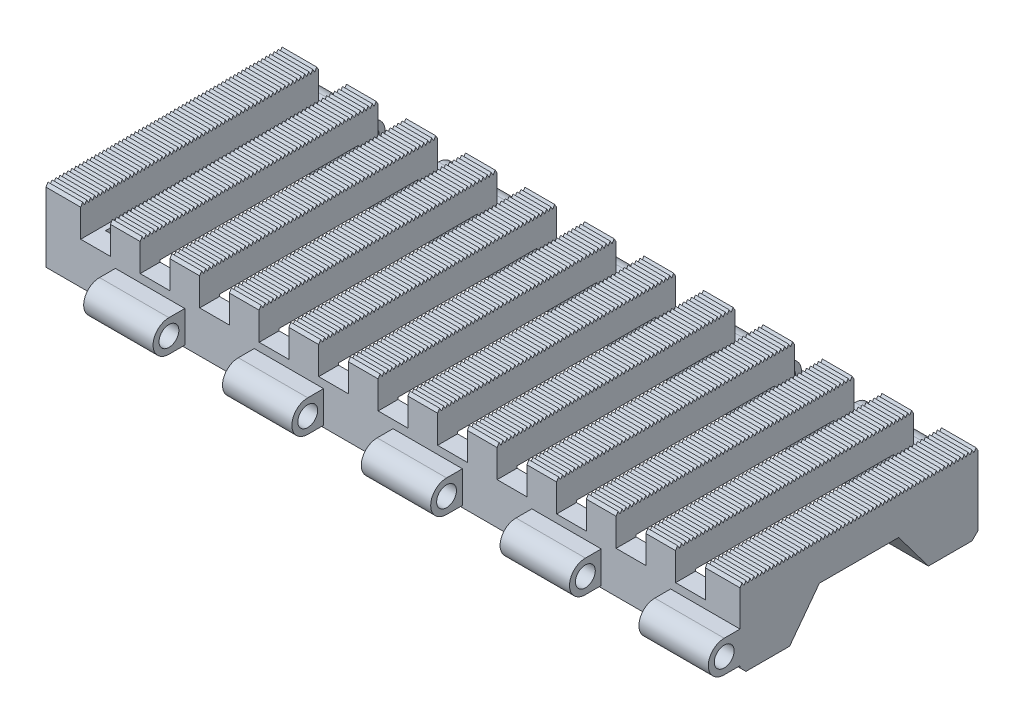
SolidWorks part; units mm, degrees
material "POM Acetal Copolymer"
ref_plane "Front Plane" through (0, 0, 0) normal (0, 0, 1) x (1, 0, 0)
ref_plane "Top Plane" through (0, 0, 0) normal (0, 1, 0) x (1, 0, 0)
ref_plane "Right Plane" through (0, 0, 0) normal (1, 0, 0) x (0, 0, -1)
sketch "Sketch1" plane through (0, 0, 0) normal (1, 0, 0) x (0, 0, -1)
  line L0 (68, 8) -> (48, 8)
  line L4 (33, -12) -> (48, 8)
  line L7 (68, 8) -> (88, 8)
  line L9 (88, 8) -> (103, -12)
  line L31 (8, 26.0025) -> (9, 27.7092)
  line L32 (9, 27.7092) -> (10, 26.0025)
  line L33 (10, 26.0025) -> (11, 27.7092)
  line L34 (11, 27.7092) -> (12, 26.0025)
  line L35 (12, 26.0025) -> (13, 27.7092)
  line L36 (13, 27.7092) -> (14, 26.0025)
  line L37 (14, 26.0025) -> (15, 27.7092)
  line L38 (15, 27.7092) -> (16, 26.0025)
  line L39 (16, 26.0025) -> (17, 27.7092)
  line L40 (17, 27.7092) -> (18, 26.0025)
  line L41 (18, 26.0025) -> (19, 27.7092)
  line L42 (19, 27.7092) -> (20, 26.0025)
  line L43 (20, 26.0025) -> (21, 27.7092)
  line L44 (21, 27.7092) -> (22, 26.0025)
  line L45 (22, 26.0025) -> (23, 27.7092)
  line L46 (23, 27.7092) -> (24, 26.0025)
  line L47 (24, 26.0025) -> (25, 27.7092)
  line L48 (25, 27.7092) -> (26, 26.0025)
  line L49 (26, 26.0025) -> (27, 27.7092)
  line L50 (27, 27.7092) -> (28, 26.0025)
  line L51 (28, 26.0025) -> (29, 27.7092)
  line L52 (29, 27.7092) -> (30, 26.0025)
  line L53 (30, 26.0025) -> (31, 27.7092)
  line L54 (31, 27.7092) -> (32, 26.0025)
  line L55 (32, 26.0025) -> (33, 27.7092)
  line L56 (33, 27.7092) -> (34, 26.0025)
  line L57 (34, 26.0025) -> (35, 27.7092)
  line L58 (35, 27.7092) -> (36, 26.0025)
  line L59 (36, 26.0025) -> (37, 27.7092)
  line L60 (37, 27.7092) -> (38, 26.0025)
  line L61 (38, 26.0025) -> (39, 27.7092)
  line L62 (39, 27.7092) -> (40, 26.0025)
  line L63 (40, 26.0025) -> (41, 27.7092)
  line L64 (41, 27.7092) -> (42, 26.0025)
  line L65 (42, 26.0025) -> (43, 27.7092)
  line L66 (43, 27.7092) -> (44, 26.0025)
  line L67 (44, 26.0025) -> (45, 27.7092)
  line L68 (45, 27.7092) -> (46, 26.0025)
  line L69 (46, 26.0025) -> (47, 27.7092)
  line L70 (47, 27.7092) -> (48, 26.0025)
  line L71 (48, 26.0025) -> (49, 27.7092)
  line L72 (49, 27.7092) -> (50, 26.0025)
  line L73 (50, 26.0025) -> (51, 27.7092)
  line L74 (51, 27.7092) -> (52, 26.0025)
  line L75 (52, 26.0025) -> (53, 27.7092)
  line L76 (53, 27.7092) -> (54, 26.0025)
  line L77 (54, 26.0025) -> (55, 27.7092)
  line L78 (55, 27.7092) -> (56, 26.0025)
  line L79 (56, 26.0025) -> (57, 27.7092)
  line L80 (57, 27.7092) -> (58, 26.0025)
  line L81 (58, 26.0025) -> (59, 27.7092)
  line L82 (59, 27.7092) -> (60, 26.0025)
  line L83 (60, 26.0025) -> (61, 27.7092)
  line L84 (61, 27.7092) -> (62, 26.0025)
  line L85 (62, 26.0025) -> (63, 27.7092)
  line L86 (63, 27.7092) -> (64, 26.0025)
  line L87 (64, 26.0025) -> (65, 27.7092)
  line L88 (65, 27.7092) -> (66, 26.0025)
  line L89 (66, 26.0025) -> (67, 27.7092)
  line L90 (67, 27.7092) -> (68, 26.0025)
  line L91 (68, 26.0025) -> (69, 27.7092)
  line L92 (69, 27.7092) -> (70, 26.0025)
  line L93 (70, 26.0025) -> (71, 27.7092)
  line L94 (71, 27.7092) -> (72, 26.0025)
  line L95 (72, 26.0025) -> (73, 27.7092)
  line L96 (73, 27.7092) -> (74, 26.0025)
  line L97 (74, 26.0025) -> (75, 27.7092)
  line L98 (75, 27.7092) -> (76, 26.0025)
  line L99 (76, 26.0025) -> (77, 27.7092)
  line L100 (77, 27.7092) -> (78, 26.0025)
  line L101 (78, 26.0025) -> (79, 27.7092)
  line L102 (79, 27.7092) -> (80, 26.0025)
  line L103 (80, 26.0025) -> (81, 27.7092)
  line L104 (81, 27.7092) -> (82, 26.0025)
  line L105 (82, 26.0025) -> (83, 27.7092)
  line L106 (83, 27.7092) -> (84, 26.0025)
  line L107 (84, 26.0025) -> (85, 27.7092)
  line L108 (85, 27.7092) -> (86, 26.0025)
  line L109 (86, 26.0025) -> (87, 27.7092)
  line L110 (87, 27.7092) -> (88, 26.0025)
  line L111 (88, 26.0025) -> (89, 27.7092)
  line L112 (89, 27.7092) -> (90, 26.0025)
  line L113 (90, 26.0025) -> (91, 27.7092)
  line L114 (91, 27.7092) -> (92, 26.0025)
  line L115 (92, 26.0025) -> (93, 27.7092)
  line L116 (93, 27.7092) -> (94, 26.0025)
  line L117 (94, 26.0025) -> (95, 27.7092)
  line L118 (95, 27.7092) -> (96, 26.0025)
  line L119 (96, 26.0025) -> (97, 27.7092)
  line L120 (97, 27.7092) -> (98, 26.0025)
  line L121 (98, 26.0025) -> (99, 27.7092)
  line L122 (99, 27.7092) -> (100, 26.0025)
  line L123 (100, 26.0025) -> (101, 27.7092)
  line L124 (101, 27.7092) -> (102, 26.0025)
  line L125 (102, 26.0025) -> (103, 27.7092)
  line L126 (103, 27.7092) -> (104, 26.0025)
  line L127 (104, 26.0025) -> (105, 27.7092)
  line L128 (105, 27.7092) -> (106, 26.0025)
  line L129 (106, 26.0025) -> (107, 27.7092)
  line L130 (107, 27.7092) -> (108, 26.0025)
  line L131 (108, 26.0025) -> (109, 27.7092)
  line L132 (109, 27.7092) -> (110, 26.0025)
  line L133 (110, 26.0025) -> (111, 27.7092)
  line L134 (111, 27.7092) -> (112, 26.0025)
  line L135 (112, 26.0025) -> (113, 27.7092)
  line L136 (113, 27.7092) -> (114, 26.0025)
  line L137 (114, 26.0025) -> (115, 27.7092)
  line L138 (115, 27.7092) -> (116, 26.0025)
  line L139 (116, 26.0025) -> (117, 27.7092)
  line L140 (117, 27.7092) -> (118, 26.0025)
  line L141 (118, 26.0025) -> (119, 27.7092)
  line L142 (119, 27.7092) -> (120, 26.0025)
  line L143 (120, 26.0025) -> (121, 27.7092)
  line L144 (121, 27.7092) -> (122, 26.0025)
  line L145 (122, 26.0025) -> (123, 27.7092)
  line L146 (123, 27.7092) -> (124, 26.0025)
  line L147 (124, 26.0025) -> (125, 27.7092)
  line L148 (125, 27.7092) -> (126, 26.0025)
  line L149 (126, 26.0025) -> (127, 27.7092)
  line L150 (127, 27.7092) -> (128, 26.0025)
  line L164 (8, -8.0025) -> (0, -8.0025)
  line L165 (0, 8.0025) -> (8, 8.0025)
  line L166 (8, 8.0025) -> (8, 26.0025)
  line L167 (136, 8) -> (128, 8)
  line L170 (128, -9) -> (125, -12)
  line L171 (136, -8) -> (128, -8)
  line L172 (125, -12) -> (103, -12)
  line L173 (128, -8) -> (128, -9)
  line L174 (33, -12) -> (11, -12)
  line L175 (8, -8.0025) -> (8, -9)
  line L176 (8, -9) -> (11, -12)
  line L177 (128, 8) -> (128, 26.0025)
  circle A0 centre (0, 0) radius 5
  arc A1 (0, 8.0025) -> (0, -8.0025) centre (0, 0) ccw
  circle A2 centre (136, 0) radius 5
  arc A3 (136, 8) -> (136, -8) centre (136, 0) cw
extrude "Boss-Extrude1" add sketch "Sketch1" along normal blind 350 contours L31 L32 L33 L34 L35 L36 L37 L38 L39 L40 L41 L42 L43 L44 L45 L46 L47 L48 L49 L50 L51 L52 L53 L54 L55 L56 L57 L58 L59 L60 L61 L62 L63 L64 L65 L66 L67 L68 L69 L70 L71 L72 L73 L74 L75 L76 L77 L78 L79 L80 L81 L82 L83 L84 L85 L86 L87 L88 L89 L90 L91 L92 L93 L94 L95 L96 L97 L98 L99 L100 L101 L102 L103 L104 L105 L106 L107 L108 L109 L110 L111 L112 L113 L114 L115 L116 L117 L118 L119 L120 L121 L122 L123 L124 L125 L126 L127 L128 L129 L130 L131 L132 L133 L134 L135 L136 L137 L138 L139 L140 L141 L142 L143 L144 L145 L146 L147 L148 L149 L150 L177 L167 A3 L171 L173 L170 L172 L9 L7 L0 L4 L174 L176 L175 L164 A1 L165 L166
extrude "Cut-Extrude2" cut sketch "Sketch1<3>" along normal blind 350 flip side to cut
sketch "Sketch1<3>" plane through (0, 0, 0) normal (1, 0, 0) x (0, 0, -1) same geometry as "Sketch1"
sketch "Sketch13" plane through (0, -12, 0) normal (0, -1, 0) x (1, 0, 0)
  line L0 (20, -118) -> (20, -18)
  line L1 (20, -11) -> (0, -11)
  line L2 (20, -11) -> (20, -18)
  line L3 (350, -11) -> (0, -11) construction
  line L4 (20, -18) -> (330, -18)
  line L5 (330, -18) -> (330, -118)
  line L6 (330, -118) -> (20, -118)
  line L7 (0, -11) -> (0, -8)
  line L8 (0, -8) -> (35, -8)
  line L9 (0, -8) -> (0, 10.7126)
  line L10 (0, 10.7126) -> (350, 10.7126)
  line L11 (35, -8) -> (35, 10.7126)
  line L12 (35, -8) -> (70, -8)
  line L13 (70, -8) -> (105, -8)
  line L14 (105, -8) -> (140, -8)
  line L15 (140, -8) -> (175, -8)
  line L16 (175, -8) -> (210, -8)
  line L17 (210, -8) -> (245, -8)
  line L18 (245, -8) -> (280, -8)
  line L19 (280, -8) -> (315, -8)
  line L20 (315, -8) -> (350, -8)
  line L21 (350, -8) -> (350, 10.7126)
  line L22 (70, -8) -> (70, 10.7126)
  line L23 (105, -8) -> (105, 10.7126)
  line L24 (140, -8) -> (140, 10.7126)
  line L25 (175, -8) -> (175, 10.7126)
  line L26 (210, -8) -> (210, 10.7126)
  line L27 (245, -8) -> (245, 10.7126)
  line L28 (280, -8) -> (280, 10.7126)
  line L29 (315, -8) -> (315, 10.7126)
  line L30 (20, -118) -> (20, -125)
  line L31 (350, -125) -> (0, -125) construction
  line L32 (20, -125) -> (0, -125)
  line L33 (0, -125) -> (0, -128)
  line L34 (0, -146.7126) -> (35, -146.7126)
  line L35 (0, -146.7126) -> (0, -128)
  line L36 (0, -128) -> (350, -128)
  line L37 (35, -146.7126) -> (35, -128)
  line L38 (35, -146.7126) -> (70, -146.7126)
  line L39 (70, -146.7126) -> (105, -146.7126)
  line L40 (105, -146.7126) -> (140, -146.7126)
  line L41 (140, -146.7126) -> (175, -146.7126)
  line L42 (175, -146.7126) -> (210, -146.7126)
  line L43 (210, -146.7126) -> (245, -146.7126)
  line L44 (245, -146.7126) -> (280, -146.7126)
  line L45 (280, -146.7126) -> (315, -146.7126)
  line L46 (315, -146.7126) -> (350, -146.7126)
  line L47 (350, -146.7126) -> (350, -128)
  line L48 (70, -146.7126) -> (70, -128)
  line L49 (105, -146.7126) -> (105, -128)
  line L50 (140, -146.7126) -> (140, -128)
  line L51 (175, -146.7126) -> (175, -128)
  line L52 (210, -146.7126) -> (210, -128)
  line L53 (245, -146.7126) -> (245, -128)
  line L54 (280, -146.7126) -> (280, -128)
  line L55 (315, -146.7126) -> (315, -128)
  line M6 (0, -33) -> (350, -33)
extrude "Cut-Extrude4" cut sketch "Sketch13" against normal blind 25 contours L6 L5 L0 M6 | L5 L4 L0 M6 region at (175, -12, -75.5) region at (175, -12, -25.5)
extrude "Cut-Extrude12" cut sketch "Sketch13<4>" against normal through all contours L8 L11 L10 L9 | L13 L23 L10 L22 | L15 L25 L10 L24 | L17 L27 L10 L26 | L19 L29 L10 L28 | L55 L46 L47 L36 | L44 L54 L36 L53 | L42 L52 L36 L51 | L40 L50 L36 L49 | L38 L48 L36 L37 region at (17.5, -12, 1.3563) region at (52.5, -12, -137.3563) region at (87.5, -12, 1.3563) region at (122.5, -12, -137.3563) region at (157.5, -12, 1.3563) region at (192.5, -12, -137.3563) region at (227.5, -12, 1.3563) region at (262.5, -12, -137.3563) region at (297.5, -12, 1.3563) region at (332.5, -12, -137.3563)
sketch "Sketch13<4>" plane through (0, -12, 0) normal (0, -1, 0) x (1, 0, 0) same geometry as "Sketch13"
sketch "Sketch15" plane through (0, 0, -8) normal (0, 0, 1) x (1, 0, 0)
  line L0 (17.5, 12) -> (17.5, 32)
  line L1 (122.5, 12) -> (122.5, 32)
  line L8 (17.5, 32) -> (32.5, 32)
  line L9 (32.5, 32) -> (32.5, 12)
  line L10 (32.5, 12) -> (17.5, 12)
  line L11 (32.5, 12) -> (32.5, 32)
  line L12 (32.5, 32) -> (47.5, 32)
  line L13 (47.5, 32) -> (47.5, 12)
  line L14 (47.5, 12) -> (32.5, 12)
  line L15 (47.5, 12) -> (47.5, 32)
  line L16 (47.5, 32) -> (62.5, 32)
  line L17 (62.5, 32) -> (62.5, 12)
  line L18 (62.5, 12) -> (47.5, 12)
  line L19 (62.5, 12) -> (62.5, 32)
  line L20 (62.5, 32) -> (77.5, 32)
  line L21 (77.5, 32) -> (77.5, 12)
  line L22 (77.5, 12) -> (62.5, 12)
  line L23 (77.5, 12) -> (77.5, 32)
  line L24 (77.5, 32) -> (92.5, 32)
  line L25 (92.5, 32) -> (92.5, 12)
  line L26 (92.5, 12) -> (77.5, 12)
  line L27 (92.5, 12) -> (92.5, 32)
  line L28 (92.5, 32) -> (107.5, 32)
  line L29 (107.5, 32) -> (107.5, 12)
  line L30 (107.5, 12) -> (92.5, 12)
  line L31 (107.5, 12) -> (107.5, 31.8131)
  line L32 (107.5, 31.8131) -> (122.5, 31.8131)
  line L33 (122.5, 31.8131) -> (122.5, 12)
  line L34 (122.5, 12) -> (107.5, 12)
  line L35 (122.5, 32) -> (137.5, 32)
  line L36 (137.5, 32) -> (137.5, 12)
  line L37 (137.5, 12) -> (122.5, 12)
  line L38 (137.5, 12) -> (137.5, 32.1397)
  line L39 (137.5, 32.1397) -> (152.5, 32.1397)
  line L40 (152.5, 32.1397) -> (152.5, 12)
  line L41 (152.5, 12) -> (137.5, 12)
  line L42 (152.5, 12) -> (152.5, 33.8765)
  line L43 (152.5, 33.8765) -> (167.5, 33.8765)
  line L44 (167.5, 33.8765) -> (167.5, 12)
  line L45 (167.5, 12) -> (152.5, 12)
  line L46 (167.5, 12) -> (167.5, 35.9115)
  line L47 (167.5, 35.9115) -> (182.5, 35.9115)
  line L48 (182.5, 35.9115) -> (182.5, 12)
  line L49 (182.5, 12) -> (167.5, 12)
  line L50 (182.5, 12) -> (182.5, 36.7803)
  line L51 (182.5, 36.7803) -> (197.5, 36.7803)
  line L52 (197.5, 36.7803) -> (197.5, 12)
  line L53 (197.5, 12) -> (182.5, 12)
  line L54 (197.5, 12) -> (197.5, 39.7776)
  line L55 (197.5, 39.7776) -> (212.5, 39.7776)
  line L56 (212.5, 39.7776) -> (212.5, 12)
  line L57 (212.5, 12) -> (197.5, 12)
  line L58 (212.5, 12) -> (212.5, 36.4319)
  line L59 (212.5, 36.4319) -> (227.5, 36.4319)
  line L60 (227.5, 36.4319) -> (227.5, 12)
  line L61 (227.5, 12) -> (212.5, 12)
  line L62 (227.5, 12) -> (227.5, 37.5608)
  line L63 (227.5, 37.5608) -> (242.5, 37.5608)
  line L64 (242.5, 37.5608) -> (242.5, 12)
  line L65 (242.5, 12) -> (227.5, 12)
  line L66 (242.5, 12) -> (242.5, 36.7461)
  line L67 (242.5, 36.7461) -> (257.5, 36.7461)
  line L68 (257.5, 36.7461) -> (257.5, 12)
  line L69 (257.5, 12) -> (242.5, 12)
  line L70 (257.5, 12) -> (257.5, 35.3776)
  line L71 (257.5, 35.3776) -> (272.5, 35.3776)
  line L72 (272.5, 35.3776) -> (272.5, 12)
  line L73 (272.5, 12) -> (257.5, 12)
  line L74 (272.5, 12) -> (272.5, 35.6742)
  line L75 (272.5, 35.6742) -> (287.5, 35.6742)
  line L76 (287.5, 35.6742) -> (287.5, 12)
  line L77 (287.5, 12) -> (272.5, 12)
  line L78 (287.5, 12) -> (287.5, 34.6036)
  line L79 (287.5, 34.6036) -> (302.5, 34.6036)
  line L80 (302.5, 34.6036) -> (302.5, 12)
  line L81 (302.5, 12) -> (287.5, 12)
  line L82 (302.5, 12) -> (302.5, 32.141)
  line L83 (302.5, 32.141) -> (317.5, 32.141)
  line L84 (317.5, 32.141) -> (317.5, 12)
  line L85 (317.5, 12) -> (302.5, 12)
  line L86 (317.5, 12) -> (317.5, 31.6092)
  line L87 (317.5, 31.6092) -> (332.5, 31.6092)
  line L88 (332.5, 31.6092) -> (332.5, 12)
  line L89 (332.5, 12) -> (317.5, 12)
  line M3 (350, 26.0025) -> (0, 26.0025)
extrude "Cut-Extrude18" cut sketch "Sketch15" against normal through all contours L9 L8 L0 M3 | L10 L9 L0 M3 | L18 L17 L13 M3 | L17 L16 L13 M3 | L26 L25 L21 M3 | L25 L24 L21 M3 | L34 L1 L29 M3 | L32 L29 L1 M3 | L41 L40 L36 M3 | L40 L39 L38 L36 M3 | L49 L48 L44 M3 | L48 L47 L46 L44 M3 | L57 L56 L52 M3 | L56 L55 L54 L52 M3 | L65 L64 L60 M3 | L64 L63 L62 L60 M3 | L73 L72 L68 M3 | L72 L71 L68 M3 | L81 L80 L76 M3 | L80 L79 L76 M3 | L89 L88 L84 M3 | L88 L87 L84 M3 region at (25, 19.0012, -8) region at (25, 29.0012, -8) region at (55, 19.0012, -8) region at (55, 29.0012, -8) region at (85, 19.0012, -8) region at (85, 29.0012, -8) region at (115, 19.0012, -8) region at (115, 28.9078, -8) region at (145, 19.0012, -8) region at (145, 29.0711, -8) region at (175, 19.0012, -8) region at (175, 30.957, -8) region at (205, 19.0012, -8) region at (205, 32.89, -8) region at (235, 19.0012, -8) region at (235, 31.7816, -8) region at (265, 19.0012, -8) region at (265, 30.69, -8) region at (295, 19.0012, -8) region at (295, 30.303, -8) region at (325, 19.0012, -8) region at (325, 28.8058, -8)
